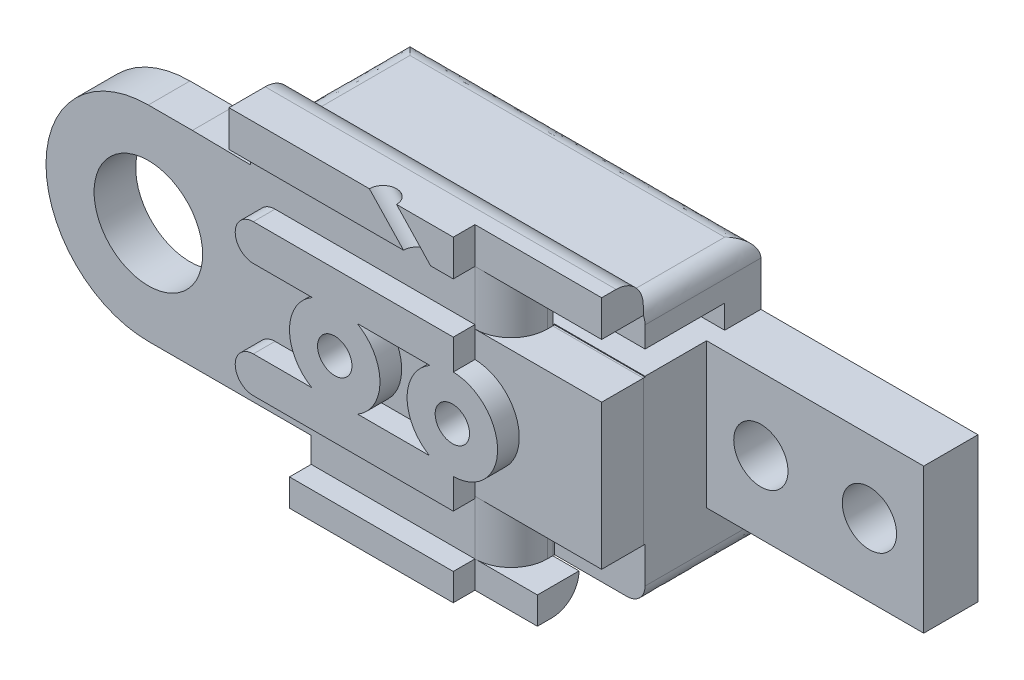
SolidWorks part; units mm, degrees
ref_plane "Front Plane" through (0, 0, 0) normal (0, 0, 1) x (1, 0, 0)
ref_plane "Top Plane" through (0, 0, 0) normal (0, 1, 0) x (1, 0, 0)
ref_plane "Right Plane" through (0, 0, 0) normal (1, 0, 0) x (0, 0, -1)
sketch "Sketch3" plane through (0, 0, 0) normal (0, 0, 1) x (1, 0, 0)
  line L7 (8, 0) -> (9, -2.5431)
  line L13 (0, 7) -> (0, 7.5) construction
  line L14 (0, 7.5) -> (-22.3287, 7.5) construction
  line L15 (0, 5.3) -> (-14, 5.3) construction
  line L16 (0, 4) -> (-14, 4) construction
  line L17 (-14, 4) -> (-14, 5.3) construction
  line L18 (5.6569, 5.6569) -> (5.6569, 7.4569)
  line L19 (5.6569, 7.4569) -> (25.0503, 7.4569)
  line L20 (21.5, -7.0431) -> (9, -7.0431)
  line L21 (9, -7.0431) -> (9, -2.5431)
  line L24 (21.5, -7.0431) -> (25.0503, -7.0431)
  line L25 (25.0503, -7.0431) -> (25.0503, 7.4569)
  arc A4 (8, 0) -> (5.6569, 5.6569) centre (0, 0) ccw
  circle A6 centre (0, 0) radius 7 construction
  circle A7 centre (0, 0) radius 3.9 construction
  circle A8 centre (0, 0) radius 5.3 construction
  circle A9 centre (0, 0) radius 4 construction
  dimension "D3" = 16.0503
  dimension "D4" = 14.5
  dimension "D2" = 5.6569
  dimension "D7" = 4.5
  dimension "D8" = 1
  dimension "D9" = 45
  dimension "D11" = 1.8
extrude "Boss-Extrude1" add sketch "Sketch3" along normal blind 2 contours L19 L25 L24 L20 L21 L7 A4 L18
sketch "Sketch20" plane through (0, 0, 0) normal (0, 0, 1) x (1, 0, 0)
  line L0 (0, 7) -> (0, 7.5) construction
  line L1 (0, 7.5) -> (-19.4737, 7.5) construction
  line L2 (0, 5.3) -> (-14, 5.3) construction
  line L3 (0, 4) -> (-14, 4) construction
  line L4 (-14, 4) -> (-14, 5.3) construction
  line L5 (0, 5.3) -> (17.4849, 5.3) construction
  line L6 (17.4849, 5.3) -> (17.4849, 4) construction
  line L7 (17.4849, 4) -> (0, 4) construction
  line L8 (-2.5, 7.5) -> (-2.5, 2.868) construction
  circle A0 centre (0, 0) radius 7 construction
  circle A1 centre (0, 0) radius 3.9 construction
  circle A3 centre (0, 0) radius 5.3 construction
  circle A4 centre (0, 0) radius 4 construction
  circle A5 centre (0, 0) radius 2 construction
  dimension "D1" = 0
  dimension "D2" = 2.5
ref_plane "Plane1" through (0, 0, 2) normal (0, 0, 1) x (1, 0, 0)
sketch "Sketch4" plane through (0, 0, 2) normal (0, 0, 1) x (1, 0, 0)
  line L4 (5.6569, 5.6569) -> (5.6569, 7.5)
  line L5 (5.6569, 5.6569) -> (5.6569, 7.4569) construction
  line L6 (5.6569, 7.5) -> (21.5, 7.5)
  line L10 (8, 0) -> (9, -2.5431)
  line L11 (9, -2.5431) -> (9, -7.0431)
  line L12 (9, -7.0431) -> (21.5, -7.0431)
  line L13 (21.5, -7.0431) -> (21.5, 7.5)
  arc A0 (8, 0) -> (5.6569, 5.6569) centre (0, 0) ccw construction
  arc A3 (8, 0) -> (5.6569, 5.6569) centre (0, 0) ccw
sketch "Sketch22" plane through (0, 0, 2) normal (0, 0, 1) x (1, 0, 0)
  line L1 (5.6569, 7.4569) -> (21.5, 7.4569)
  line L6 (8, 0) -> (9, -2.5431)
  line L7 (9, -2.5431) -> (9, -7.0431)
  line L8 (9, -7.0431) -> (25.0503, -7.0431)
  line L10 (21.5, 7.4569) -> (25.0503, 7.4569)
  line L16 (5.6569, 7.4569) -> (5.6569, 5.6569)
  line L17 (25.0503, 7.4569) -> (25.0503, -7.0431)
  arc A0 (8, 0) -> (5.6569, 5.6569) centre (0, 0) ccw
extrude "Boss-Extrude6" add sketch "Sketch22" along normal blind 4.5
sketch "Sketch25" plane through (0, 0, 2) normal (0, 0, 1) x (1, 0, 0)
  line L0 (0, 5.3) -> (18.0981, 5.3) construction
  line L1 (0, 4) -> (18.0981, 4) construction
  line L2 (18.0981, 4) -> (18.0981, 5.3) construction
sketch "Sketch26" plane through (0, 0, 2) normal (0, 0, 1) x (1, 0, 0)
  line L1 (18.0981, 5.3) -> (2.5301, 5.3)
  line L2 (18.0981, 4) -> (2.5301, 4)
  line L3 (2.5301, 5.3) -> (2.5301, 4)
  line L4 (18.0981, 5.3) -> (25.0503, 5.3)
  line L6 (25.0503, 5.3) -> (25.0503, 4)
  line L7 (25.0503, 4) -> (18.0981, 4)
  line L8 (25.0503, -7.0431) -> (25.0503, 7.4569) construction
extrude "Cut-Extrude6" cut sketch "Sketch26" along normal blind 4.5
ref_plane "Plane18" through (0, 0, 6.5) normal (0, 0, 1) x (1, 0, 0)
sketch "Sketch31" plane through (0, 0, 6.5) normal (0, 0, 1) x (1, 0, 0)
  line L0 (2.4327, 5.6569) -> (0.0002, 5.6569)
  line L4 (9, -5.6569) -> (0, -5.6569)
  line L7 (2.4327, 5.6569) -> (5.6569, 5.6137)
  line L8 (5.6569, 5.6137) -> (5.6569, 7.4569)
  line L12 (9, -7.0431) -> (9, -5.6569)
  line L13 (9, -2.5431) -> (9, -7.0431) construction
  line L22 (5.6569, 7.4569) -> (5.6569, 8.9569)
  line L23 (5.6569, 8.9569) -> (25.0503, 8.9569)
  line L25 (9, -7.0431) -> (9, -8.5431)
  line L26 (9, -8.5431) -> (21.5, -8.5431)
  line L27 (21.5, -8.5431) -> (21.5, -7.0431)
  line L28 (21.5, -7.0431) -> (25.0503, -7.0431)
  line L29 (25.0503, -7.0431) -> (25.0503, 8.9569)
  line L31 (25.0503, 7.4569) -> (5.6569, 7.4569) construction
  arc A0 (0.0002, 5.6569) -> (0, -5.6569) centre (0, 0) ccw
  dimension "D1" = 5.6569
  dimension "D2" = 5.6569
  dimension "D3" = 1.5
  dimension "D4" = 17.5
  dimension "D5" = 1.5
  dimension "D6" = 3.3431
extrude "Boss-Extrude14" add sketch "Sketch31" along normal blind 2.3 separate body
sketch "Sketch32" plane through (0, 0, 8.8) normal (0, 0, 1) x (1, 0, 0)
  circle A0 centre (0, 0) radius 3
  dimension "D1" = 6
extrude "Cut-Extrude7" cut sketch "Sketch32" against normal blind 2.3
sketch "Sketch33" plane through (0, 0, 8.8) normal (0, 0, 1) x (1, 0, 0)
  line L1 (5.6569, 8.9569) -> (5.6569, 6.9569)
  line L4 (9, -7.0431) -> (9, -8.5431)
  line L7 (7, -4.1569) -> (18.0503, -4.1569)
  line L11 (9, -8.5431) -> (18.0503, -8.5431)
  line L15 (18.0503, -8.5431) -> (18.0503, -7.0431)
  line L16 (18.0503, -7.0431) -> (9, -7.0431)
  line L17 (5.6569, 8.9569) -> (18.0503, 8.9569)
  line L18 (25.0503, 8.9569) -> (5.6569, 8.9569) construction
  line L21 (18.0503, 6.9569) -> (18.0503, 8.9569)
  line L22 (18.0503, -4.1569) -> (18.0503, -2.1569)
  line L23 (18.0503, -2.1569) -> (7, -2.1569)
  line L27 (5.6569, 6.9569) -> (18.0503, 6.9569)
  line L28 (18.0503, 2.172) -> (7, 2.172)
  line L30 (7, 4.172) -> (18.0503, 4.172)
  line L33 (18.0503, 2.172) -> (18.0503, 4.172)
  line L35 (9, -8.5431) -> (21.5, -8.5431) construction
  line L36 (25.0503, -7.0431) -> (25.0503, 8.9569) construction
  arc A1 (7, -2.1569) -> (7, -4.1569) centre (7, -3.1569) ccw
  arc A2 (7, 4.172) -> (7, 2.172) centre (7, 3.172) ccw
  dimension "D1" = 7
  dimension "D2" = 2
  dimension "D3" = 2
  dimension "D4" = 1.5
  dimension "D5" = 2
extrude "Boss-Extrude15" add sketch "Sketch33" along normal blind 1.2
sketch "Sketch35" plane through (0, 0, 8.8) normal (0, 0, 1) x (1, 0, 0)
  line L0 (25.0503, 3.9569) -> (25.0503, 6.9569)
  line L1 (25.0503, 3.9569) -> (20.0503, 3.9569)
  line L2 (25.0503, 6.9569) -> (20.0503, 6.9569)
  line L3 (20.0503, 3.9569) -> (20.0503, 6.9569)
  line L5 (25.0503, -7.0431) -> (25.0503, 8.9569) construction
  line L6 (25.0503, -7.0431) -> (20.0503, -7.0431)
  line L7 (25.0503, -7.0431) -> (25.0503, -4.0431)
  line L8 (20.0503, -7.0431) -> (20.0503, -4.0431)
  line L9 (25.0503, -4.0431) -> (20.0503, -4.0431)
  line L10 (18.0503, -7.0431) -> (9, -7.0431) construction
  dimension "D1" = 5
  dimension "D2" = 3
  dimension "D3" = 3
extrude "Cut-Extrude8" cut sketch "Sketch35" against normal blind 2.4
sketch "Sketch43" plane through (0, 0, 8.8) normal (0, 0, 1) x (1, 0, 0)
  line L2 (0, -5.6569) -> (9, -5.6569) construction
  circle A0 centre (11.5, 0) radius 2.5
  circle A1 centre (18, 0) radius 2.5
  dimension "D1" = 2.5
  dimension "D3" = 5
  dimension "D4" = 6.5
  dimension "D2" = 5.6569
extrude "Boss-Extrude17" add sketch "Sketch43" along normal blind 1.2
sketch "Sketch44" plane through (0, 0, 10) normal (0, 0, 1) x (1, 0, 0)
  circle A0 centre (11.5, 0) radius 0.95
  circle A1 centre (18, 0) radius 0.95
  dimension "D1" = 1.9
  dimension "D2" = 1.9
extrude "Cut-Extrude11" cut sketch "Sketch44" against normal through all both and the other way through all
sketch "Sketch45" plane through (0, 0, 0) normal (0, 0, -1) x (-1, 0, 0)
  circle A0 centre (-11.5, 0) radius 2
  circle A1 centre (-18, 0) radius 2
ref_plane "Plane17" through (0, 0, 10) normal (0, 0, 1) x (1, 0, 0)
sketch "Sketch49" plane through (0, 6.9569, 0) normal (0, -1, 0) x (1, 0, 0)
  line L0 (5.6569, 10) -> (18.0503, 10) construction
  line L1 (18.0503, 10) -> (18.0503, 8.8) construction
  circle A0 centre (16.0503, 10) radius 0.75
  dimension "D1" = 2
sketch "Sketch50" plane through (0, 0, 10) normal (0, 0, 1) x (1, 0, 0)
  line L0 (16.0503, 6.9569) -> (27.3935, -5.0795) construction
extrude "Cut-Extrude13" cut sketch "Sketch49" along direction (0.6858, -0.7278, 0) on the side against the normal blind 3
fillet "Fillet1" radius 1.5 2 edges at (15.3536, 8.9569, 6.5) (15.25, -8.5431, 6.5)
fillet "Fillet3" radius 1 6 edges at (9, -7.0431, 3.25) (5.6569, 7.4569, 3.25) (17.0251, -7.0431, 0) (15.3536, 7.4569, 0) (25.0503, -7.0431, 3.2) (25.0503, 7.4569, 3.25) first distance on face at (18.0335, -7.0431, 4.3) first distance on face at (5.6569, 6.5569, 3.25) first distance on face at (12.45, 0, 0) first distance on face at (25.0503, 2.3692, 4.8857)
extrude "Cut-Extrude15" cut sketch "Sketch45" against normal blind 4
fillet "Fillet4" radius 2 2 edges at (20.0503, -5.5431, 8.8) (20.0503, 5.4569, 8.8)
sketch "Sketch51" plane through (25.0503, 0, 0) normal (1, 0, 0) x (0, 0, -1)
  line L0 (0, 4) -> (0, -4)
  line L1 (0, 4) -> (-3, 4)
  line L2 (0, -4) -> (-3, -4)
  line L3 (-3, 4) -> (-3, -4)
  line L8 (-6.4, 4) -> (-2, 4) construction
  dimension "D1" = 8
  dimension "D2" = 3
extrude "Boss-Extrude18" add sketch "Sketch51" along normal blind 12
sketch "Sketch52" plane through (0, 0, 0) normal (0, 0, -1) x (-1, 0, 0)
  line L0 (-37.0503, -4) -> (-37.0503, 4) construction
  line L1 (-37.0503, 4) -> (-25.0503, 4) construction
  line L3 (-6.6569, 7.4569) -> (-24.0503, 7.4569) construction
  circle A0 centre (-34.0503, 0) radius 1.5
  circle A1 centre (-28.0503, 0) radius 1.5
  dimension "D1" = 6
  dimension "D2" = 3
  dimension "D3" = 4
  dimension "D4" = 7.4569
extrude "Cut-Extrude16" cut sketch "Sketch52" against normal blind 12
